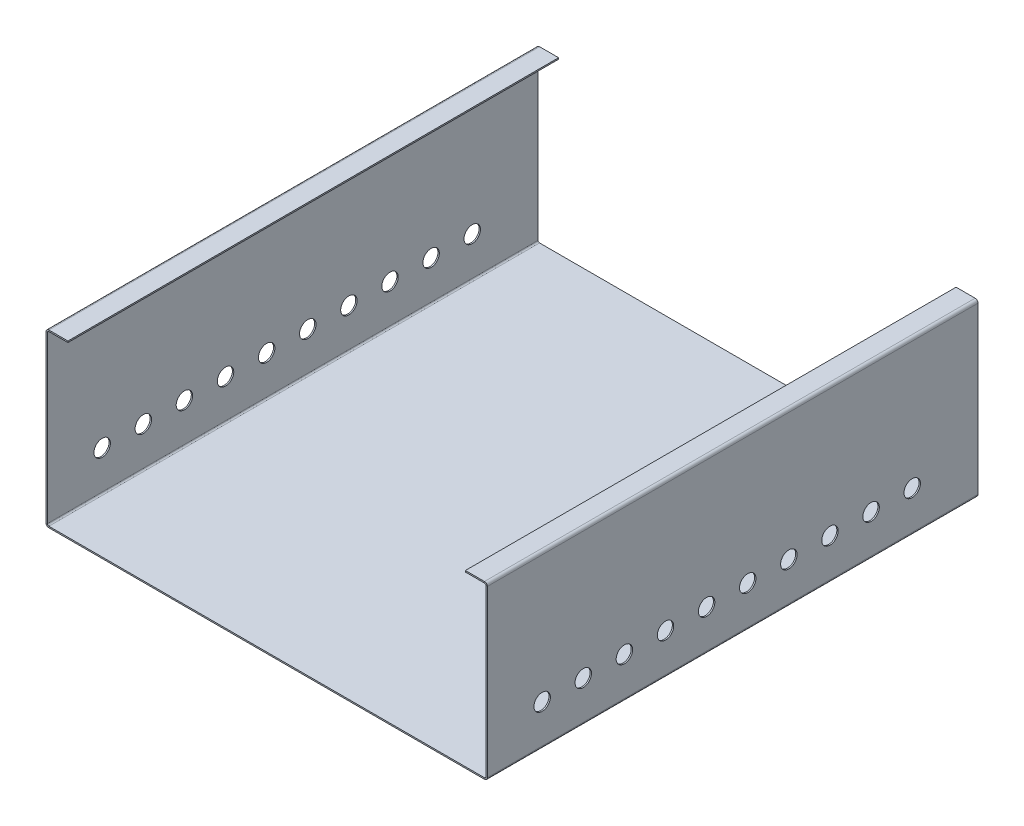
SolidWorks part; units mm, degrees
note: The reader was unsure of these and kept them because the rebuilt part matched: flange length of "Ребро-кромка1", "Ребро-кромка2".
ref_plane "Спереди" through (0, 0, 0) normal (0, 0, 1) x (1, 0, 0)
ref_plane "Сверху" through (0, 0, 0) normal (0, 1, 0) x (1, 0, 0)
ref_plane "Справа" through (0, 0, 0) normal (1, 0, 0) x (0, 0, -1)
sketch "Эскиз1" plane through (0, 0, 0) normal (0, 1, 0) x (1, 0, 0)
  line L1 (-62.4961, 42.7256) -> (257.5039, 42.7256)
  line L2 (-62.4961, 42.7256) -> (-62.4961, -315.2744)
  line L3 (-62.4961, -315.2744) -> (257.5039, -315.2744)
  line L4 (257.5039, 42.7256) -> (257.5039, -315.2744)
  dimension "D1" = 320
  dimension "D2" = 358
sheet metal parameters "Листовой металл1" thickness 1 parameters "D1"=1.1
base flange "Базовая кромка1" sketch "Эскиз1" thickness 1 reverse thickness direction no parameters "D1"=1.1
edge flange "Ребро-кромка1" sketch "Эскиз8" flange profiles "Эскиз8", "Эскиз9" flange angle 90 flange length 123 flange position material outside bend radius 1.1 thickness 1 relief rectangular parameters "D6"=10, "D8"=1
sketch "Эскиз8" plane through (-62.4961, 0, 0) normal (-1, 0, 0) x (0, 0, 1)
  line L0 (-42.7256, 0) -> (315.2744, 0) construction
  line L1 (-42.7256, 0) -> (315.2744, 0)
  line L2 (-42.7256, 0) -> (-42.7256, 123)
  line L3 (-42.7256, 123) -> (315.2744, 123)
  line L4 (315.2744, 123) -> (315.2744, 0)
sketch "Эскиз9" plane through (257.5039, 0, 0) normal (1, 0, 0) x (0, 0, -1)
  line L0 (-315.2744, 0) -> (42.7256, 0) construction
  line L1 (-315.2744, 0) -> (42.7256, 0)
  line L2 (-315.2744, 0) -> (-315.2744, 123)
  line L3 (-315.2744, 123) -> (42.7256, 123)
  line L4 (42.7256, 123) -> (42.7256, 0)
bend "EdgeBend1" bend radius 1.1 bend angle 90 parameters "D5"=1
bend "EdgeBend2" bend radius 1.1 bend angle 90 parameters "D5"=2
edge flange "Ребро-кромка2" sketch "Эскиз14" flange profiles "Эскиз14", "Эскиз15" flange angle 90 flange length 15 flange position material outside bend radius 1.1 thickness 1 relief rectangular parameters "D6"=10, "D8"=1
sketch "Эскиз14" plane through (-62.4961, 123, 0) normal (0, 1, 0) x (0, 0, 1)
  line L0 (315.2744, 0) -> (-42.7256, 0) construction
  line L1 (315.2744, 0) -> (-42.7256, 0)
  line L2 (-42.7256, 0) -> (-42.7256, 15)
  line L3 (-42.7256, 15) -> (315.2744, 15)
  line L4 (315.2744, 15) -> (315.2744, 0)
sketch "Эскиз15" plane through (257.5039, 123, 0) normal (0, 1, 0) x (0, 0, -1)
  line L0 (42.7256, 0) -> (-315.2744, 0) construction
  line L1 (42.7256, 0) -> (-315.2744, 0)
  line L2 (-315.2744, 0) -> (-315.2744, 15)
  line L3 (-315.2744, 15) -> (42.7256, 15)
  line L4 (42.7256, 15) -> (42.7256, 0)
bend "EdgeBend3" bend radius 1.1 bend angle 90 parameters "D5"=3
bend "EdgeBend4" bend radius 1.1 bend angle 90 parameters "D5"=4
sketch "Эскиз16" plane through (258.5039, 0, 0) normal (1, 0, 0) x (0, 0, -1)
  line L0 (-290.0236, 29) -> (24.2481, 29) construction
  line L1 (-315.2744, 121.9) -> (-315.2744, 1.1) construction
  line L2 (42.7256, -1) -> (-315.2744, -1) construction
  circle A0 centre (-275.2744, 29) radius 6
  circle A1 centre (-245.2744, 29) radius 6
  circle A2 centre (-215.2744, 29) radius 6
  circle A3 centre (-185.2744, 29) radius 6
  circle A4 centre (-155.2744, 29) radius 6
  circle A5 centre (-125.2744, 29) radius 6
  circle A6 centre (-95.2744, 29) radius 6
  circle A7 centre (-65.2744, 29) radius 6
  circle A8 centre (-35.2744, 29) radius 6
  circle A9 centre (-5.2744, 29) radius 6
  dimension "D1" = 40
  dimension "D2" = 30
  dimension "D3" = 12
  dimension "D4" = 10
extrude "Вырез-Вытянуть1" cut sketch "Эскиз16" against normal blind 334 normal cut yes
flat pattern "Развертка1" [suppressed]
sketch "Сгиб-Линии1" plane through (0, 0, 0) normal (0, 1, 0) x (1, 0, 0)
sketch3d "Граничная рамка1" [suppressed]
  line L0 (-241.5039, -261.2744, 0) -> (62.4961, -261.2744, 0) construction
  line L1 (-241.5039, 42.7256, 0) -> (62.4961, 42.7256, 0) construction
  line L2 (-241.5039, -261.2744, 0) -> (-241.5039, 42.7256, 0) construction
  line L3 (62.4961, -261.2744, 0) -> (62.4961, 42.7256, 0) construction
bend of the flat pattern "Плоское состояние-<EdgeBend1>1"
bend of the flat pattern "Плоское состояние-<EdgeBend2>1"
bend of the flat pattern "Плоское состояние-<EdgeBend3>1"
bend of the flat pattern "Плоское состояние-<EdgeBend4>1"
